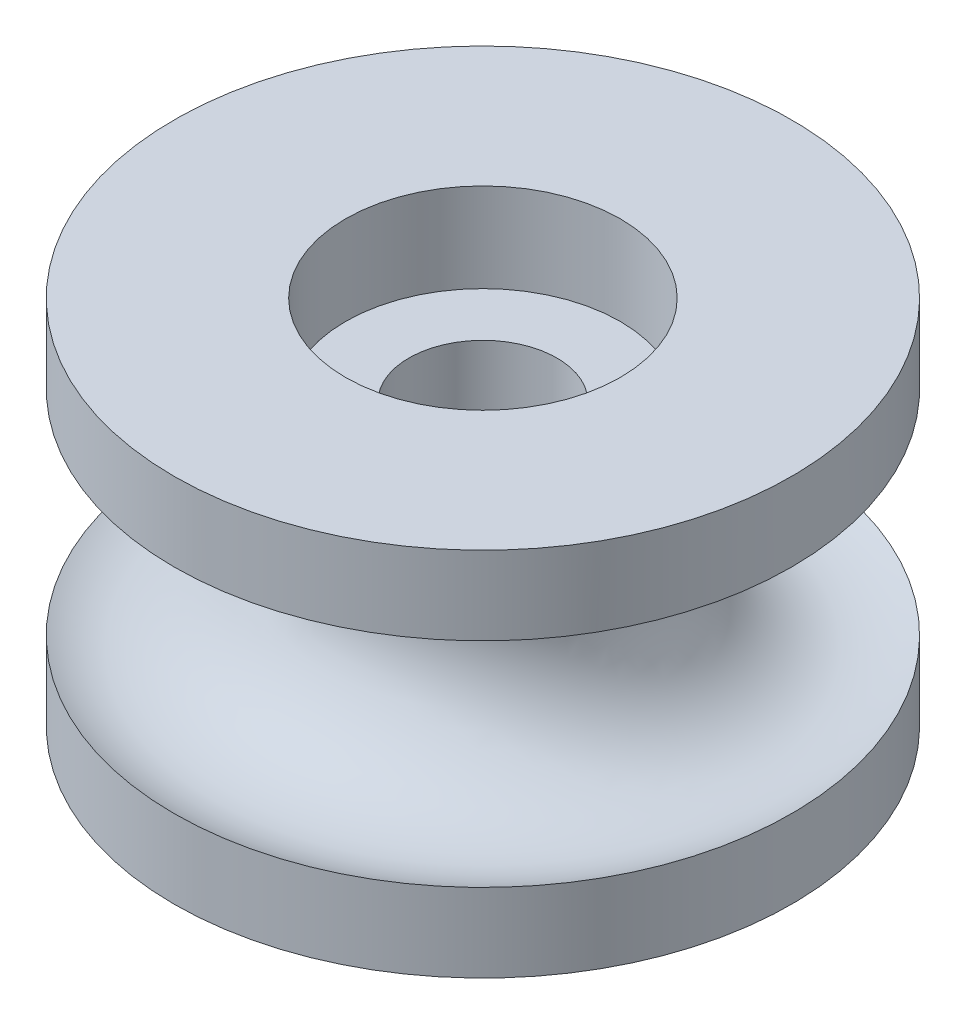
SolidWorks part; units mm, degrees
ref_plane "Front Plane" through (0, 0, 0) normal (0, 0, 1) x (1, 0, 0)
ref_plane "Top Plane" through (0, 0, 0) normal (0, 1, 0) x (1, 0, 0)
ref_plane "Right Plane" through (0, 0, 0) normal (1, 0, 0) x (0, 0, -1)
sketch "Sketch1" plane through (0, 0, 0) normal (0, 1, 0) x (1, 0, 0)
  circle A0 centre (0, 0) radius 6
  circle A1 centre (0, 0) radius 25
  dimension "D1" = 12
  dimension "D2" = 50
extrude "Boss-Extrude1" add sketch "Sketch1" along normal blind 15 and the other way blind 15
sketch "Sketch2" plane through (0, 0, 0) normal (1, 0, 0) x (0, 0, -1)
  line L0 (0, 0) -> (21, 0) construction
  line L4 (0, 0) -> (0, 15) construction
  line L5 (6, 15) -> (-6, 15) construction
  circle A1 centre (21, 0) radius 9.525
  dimension "D1" = 19.05
  dimension "D2" = 21
revolve "Cut-Revolve1" cut sketch "Sketch2" angle 360 about L4
sketch "Sketch3" plane through (0, 0, 0) normal (0, 1, 0) x (1, 0, 0)
  circle A0 centre (0, 0) radius 11.125
  dimension "D1" = 22.25
extrude "Cut-Extrude1" cut sketch "Sketch3" against normal blind 7.2 from surface starting at face at (0, 15, 25)
sketch "Sketch4" plane through (0, 0, 0) normal (0, 1, 0) x (1, 0, 0)
  circle A0 centre (0, 0) radius 11.125 construction
  circle A1 centre (0, 0) radius 11.125
extrude "Cut-Extrude2" cut sketch "Sketch4" along normal blind 7.2 from surface starting at face at (0, -15, 6)
